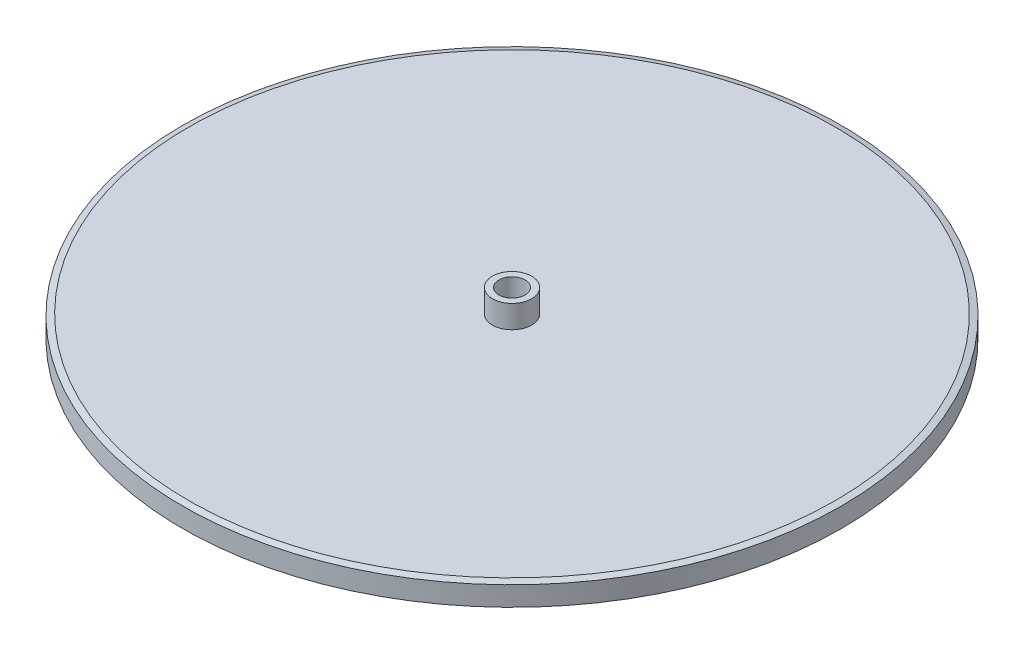
SolidWorks part; units mm, degrees
material "Сталь ШХ15 ГОСТ 801-78"
ref_plane "Plane1" through (0, 0, 0) normal (0, 0, 1) x (1, 0, 0)
ref_plane "Plane2" through (0, 0, 0) normal (0, 1, 0) x (1, 0, 0)
ref_plane "Plane3" through (0, 0, 0) normal (1, 0, 0) x (0, 0, -1)
sketch "Эскиз1" plane through (0, 0, 0) normal (0, 0, 1) x (1, 0, 0)
  line L0 (0, 0) -> (50.5, 0)
  line L1 (50.5, 0) -> (50.5, 3.5)
  line L2 (50.5, 3.5) -> (3, 3.5)
  line L3 (3, 3.5) -> (3, 7)
  line L4 (3, 7) -> (0, 7)
  line L5 (0, 7) -> (0, 0)
  dimension "D1" = 3.5
  dimension "30" = 50.5
  dimension "D3" = 3
  dimension "D4" = 3.5
ref_axis "Ось1" through (0, 7, 0) along (0, -1, 0)
revolve "Повернуть2" add sketch "Эскиз1" angle 360 about axis through (0, 7, 0) along (0, -1, 0)
chamfer "Фаска1" distance 0.94 angle 15 1 edges at (-50.5, 3.5, 0) first distance on face at (-3, 3.5, 0)
chamfer "Фаска2" distance 0.94 angle 15 1 edges at (-50.5, 0, 0) first distance on face at (-50.5, 0, 0)
sketch "Эскиз2" plane through (0, 0, 0) normal (0, -1, 0) x (-1, 0, 0)
  circle A0 centre (0, 0) radius 2
  dimension "D1" = 4
sketch "Эскиз3" plane through (0, 0, 0) normal (0, 0, 1) x (1, 0, 0)
  circle A0 centre (0, 5.828) radius 1
extrude "Вырез-Вытянуть3" cut sketch "Эскиз2" against normal through all both contours A0
